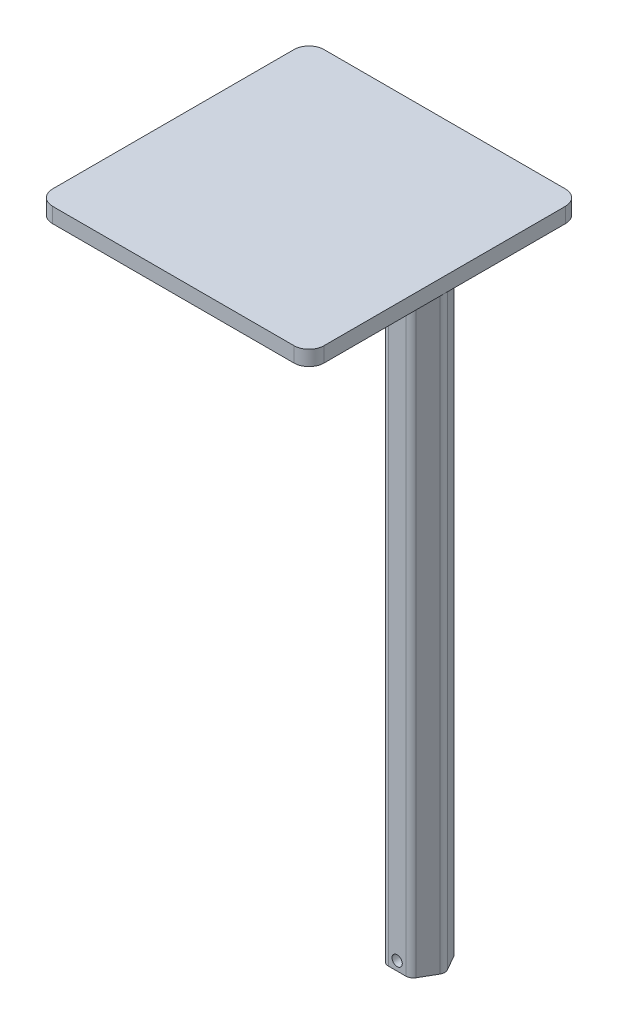
SolidWorks part; units mm, degrees
ref_plane "Front Plane" through (0, 0, 0) normal (0, 0, 1) x (1, 0, 0)
ref_plane "Top Plane" through (0, 0, 0) normal (0, 1, 0) x (1, 0, 0)
ref_plane "Right Plane" through (0, 0, 0) normal (1, 0, 0) x (0, 0, -1)
sketch "Sketch1" plane through (0, 0, 0) normal (0, 1, 0) x (1, 0, 0)
  line L1 (4.3301, 7.5) -> (-4.3301, 7.5)
  line L2 (-4.3301, 7.5) -> (-8.6603, 0)
  line L3 (-8.6603, 0) -> (-4.3301, -7.5)
  line L4 (-4.3301, -7.5) -> (4.3301, -7.5)
  line L5 (4.3301, -7.5) -> (8.6603, 0)
  line L6 (8.6603, 0) -> (4.3301, 7.5)
  circle A0 centre (0, 0) radius 7.5 construction
  dimension "D1" = 15
extrude "Boss-Extrude1" add sketch "Sketch1" along normal mid plane 200
hole_wizard "M3 Clearance Hole1" positions "Sketch4" profile "Sketch5" hole size "M3" standard "ANSI Metric" end condition up to next
sketch "Sketch4" plane through (0, 0, 7.5) normal (0, 0, 1) x (1, 0, 0)
  line L0 (-4.3301, -100) -> (4.3301, -100) construction
  point P3 (0, -97)
  point P7 (0, -100)
  dimension "D1" = 3
sketch "Sketch5" plane through (0, -97, 7.5) normal (1, 0, 0) x (0, -1, 0)
  line L0 (0, 0) -> (0, 15)
  line L1 (0, 15) -> (1.7, 15)
  line L2 (1.7, 15) -> (1.7, 0)
  line L5 (1.7, 0) -> (0, 0)
  line L11 (0, -6.35) -> (0, 107.95) construction
  dimension "Thru Hole Dia." = 3.4
  dimension "Thru Hole Depth" = 15
fillet "Fillet1" radius 2.5 6 edges at (8.6603, 0, 0) (-4.3301, 0, 7.5) (-8.6603, 0, 0) (-4.3301, 0, -7.5) (4.3301, 0, -7.5) (4.3301, 0, 7.5)
sketch "Sketch6" plane through (0, 100, 0) normal (0, 1, 0) x (1, 0, 0)
  line L1 (8.2735, 45) -> (-81.7265, 45)
  line L2 (8.2735, 45) -> (8.2735, -45)
  line L3 (8.2735, -45) -> (-81.7265, -45)
  line L4 (-81.7265, 45) -> (-81.7265, -45)
  arc A1 (7.9386, -1.25) -> (7.9386, 1.25) centre (5.7735, 0) ccw construction
  point P13 (8.2735, 0)
  point P14 (8.2735, 0)
  dimension "D1" = 90
extrude "Boss-Extrude2" add sketch "Sketch6" against normal blind 5
fillet "Fillet2" radius 5 4 edges at (8.2735, 97.5, 45) (8.2735, 97.5, -45) (-81.7265, 97.5, -45) (-81.7265, 97.5, 45)
